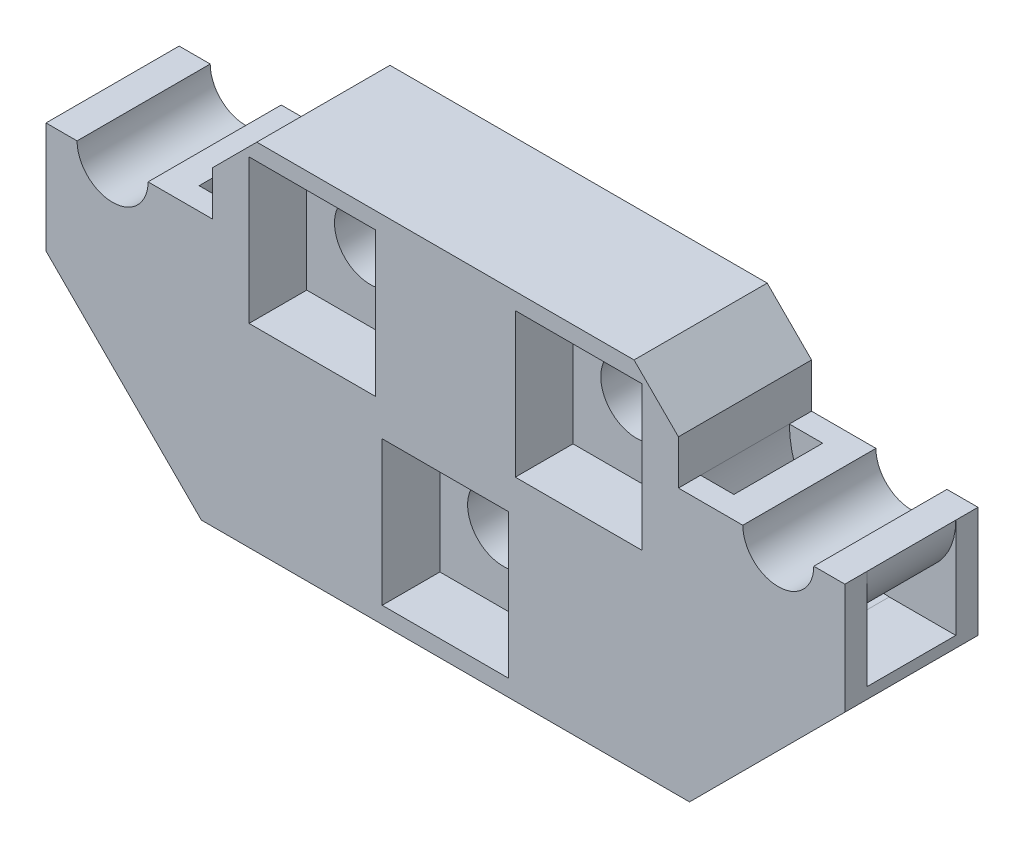
SolidWorks part; units mm, degrees
ref_plane "Front Plane" through (0, 0, 0) normal (0, 0, 1) x (1, 0, 0)
ref_plane "Top Plane" through (0, 0, 0) normal (0, 1, 0) x (1, 0, 0)
ref_plane "Right Plane" through (0, 0, 0) normal (1, 0, 0) x (0, 0, -1)
sketch "Sketch1" plane through (0, 0, 0) normal (0, 0, 1) x (1, 0, 0)
  line L1 (321.5816, 91.95) -> (357.5816, 91.95)
  line L2 (321.5816, 91.95) -> (321.5816, 75.95)
  line L3 (321.5816, 75.95) -> (357.5816, 75.95)
  line L4 (357.5816, 91.95) -> (357.5816, 75.95)
  dimension "D1" = 36
  dimension "D2" = 16
extrude "Boss-Extrude1" add sketch "Sketch1" along normal blind 6
sketch "Sketch2" plane through (0, 0, 6) normal (0, 0, 1) x (1, 0, 0)
  line L0 (357.5816, 91.95) -> (321.5816, 91.95) construction
  line L1 (357.5816, 75.95) -> (357.5816, 91.95) construction
  line L2 (321.5816, 91.95) -> (321.5816, 75.95) construction
  circle A0 centre (333.5816, 87.95) radius 1.6
  circle A1 centre (345.5816, 87.95) radius 1.6
  circle A2 centre (339.5816, 79.95) radius 1.6
  dimension "D1" = 3.2
  dimension "D2" = 3.2
  dimension "D3" = 3.2
  dimension "D4" = 4
  dimension "D5" = 4
  dimension "D6" = 8
  dimension "D7" = 12
  dimension "D8" = 12
  dimension "D9" = 18
extrude "Cut-Extrude1" cut sketch "Sketch2" against normal blind 6
chamfer "Chamfer1" distance 7 angle 45 2 edges at (357.5816, 75.95, 3) (321.5816, 75.95, 3)
sketch "Sketch4" plane through (0, 0, 6) normal (0, 0, 1) x (1, 0, 0)
  line L0 (357.5816, 91.95) -> (321.5816, 91.95) construction
  line L1 (321.5816, 91.95) -> (321.5816, 82.95) construction
  line L2 (357.5816, 82.95) -> (357.5816, 91.95) construction
  circle A0 centre (324.5816, 87.95) radius 1.6
  circle A1 centre (354.5816, 87.95) radius 1.6
  dimension "D1" = 3.2
  dimension "D2" = 3.2
  dimension "D3" = 4
  dimension "D4" = 3
  dimension "D5" = 3
  dimension "D6" = 4
extrude "Cut-Extrude2" cut sketch "Sketch4" against normal blind 6
sketch "Sketch5" plane through (0, 0, 6) normal (0, 0, 1) x (1, 0, 0)
  line L0 (321.5816, 91.95) -> (321.5816, 82.95) construction
  line L1 (321.5816, 87.95) -> (329.0816, 87.95)
  line L2 (321.5816, 87.95) -> (321.5816, 91.95)
  line L3 (321.5816, 91.95) -> (329.0816, 91.95)
  line L4 (329.0816, 87.95) -> (329.0816, 91.95)
  line L5 (357.5816, 91.95) -> (321.5816, 91.95) construction
  line L6 (357.5816, 82.95) -> (357.5816, 91.95) construction
  line L7 (357.5816, 87.95) -> (350.0816, 87.95)
  line L8 (357.5816, 87.95) -> (357.5816, 91.95)
  line L9 (357.5816, 91.95) -> (350.0816, 91.95)
  line L10 (350.0816, 87.95) -> (350.0816, 91.95)
  dimension "D1" = 7.5
  dimension "D2" = 7.5
extrude "Cut-Extrude3" cut sketch "Sketch5" against normal blind 6
chamfer "Chamfer2" distance 2 angle 45 2 edges at (350.0816, 91.95, 3) (329.0816, 91.95, 3)
sketch "Sketch6" plane through (0, 87.95, 0) normal (0, 1, 0) x (1, 0, 0)
  line L0 (329.0816, -6) -> (329.0816, 0) construction
  line L1 (329.0816, -1) -> (327.4816, -1)
  line L2 (329.0816, -1) -> (329.0816, -5)
  line L3 (329.0816, -5) -> (327.4816, -5)
  line L4 (327.4816, -1) -> (327.4816, -5)
  line L5 (350.0816, 0) -> (350.0816, -6) construction
  line L6 (350.0816, -1) -> (351.5816, -1)
  line L7 (350.0816, -1) -> (350.0816, -5)
  line L8 (350.0816, -5) -> (351.5816, -5)
  line L9 (351.5816, -1) -> (351.5816, -5)
  line L10 (326.1816, -6) -> (329.0816, -6) construction
  line L11 (350.0816, -6) -> (352.9816, -6) construction
  dimension "D1" = 4
  dimension "D2" = 1.6
  dimension "D3" = 1
  dimension "D4" = 4
  dimension "D5" = 1.5
  dimension "D6" = 1
extrude "Cut-Extrude4" cut sketch "Sketch6" against normal blind 3
sketch "Sketch7" plane through (357.5816, 0, 0) normal (1, 0, 0) x (0, 0, -1)
  line L0 (0, 82.95) -> (0, 87.95) construction
  line L1 (-5, 84.95) -> (-1, 84.95)
  line L2 (-5, 84.95) -> (-5, 83.45)
  line L3 (-5, 83.45) -> (-1, 83.45)
  line L4 (-1, 84.95) -> (-1, 83.45)
  line L5 (0, 87.95) -> (-6, 87.95) construction
  dimension "D1" = 4
  dimension "D2" = 1.5
  dimension "D3" = 1
  dimension "D4" = 3
extrude "Cut-Extrude6" cut sketch "Sketch7" against normal up to surface (7.5 mm away) up to face at (350.0816, 87.7, 3)
fillet "Fillet1" radius 3 1 edges at (351.5816, 84.95, 3)
fillet "Fillet2" radius 3 1 edges at (357.5816, 84.95, 3)
sketch "Sketch8" plane through (321.5816, 0, 0) normal (-1, 0, 0) x (0, 0, 1)
  line L0 (0, 87.95) -> (6, 87.95) construction
  line L1 (5, 84.95) -> (1, 84.95)
  line L2 (5, 84.95) -> (5, 83.45)
  line L3 (5, 83.45) -> (1, 83.45)
  line L4 (1, 84.95) -> (1, 83.45)
  line L5 (6, 87.95) -> (6, 82.95) construction
  dimension "D1" = 1.5
  dimension "D2" = 3
  dimension "D3" = 1
  dimension "D4" = 4
extrude "Cut-Extrude7" cut sketch "Sketch8" against normal up to surface (7.5 mm away) up to face at (329.0816, 87.7, 3)
fillet "Fillet3" radius 3 2 edges at (327.4816, 84.95, 3) (321.5816, 84.95, 3)
sketch "Sketch10" plane through (0, 0, 6) normal (0, 0, 1) x (1, 0, 0)
  line L1 (330.7316, 91.2) -> (336.4316, 91.2)
  line L2 (330.7316, 91.2) -> (330.7316, 84.7)
  line L3 (330.7316, 84.7) -> (336.4316, 84.7)
  line L4 (336.4316, 91.2) -> (336.4316, 84.7)
  line L5 (342.7316, 91.2) -> (348.4316, 91.2)
  line L6 (342.7316, 91.2) -> (342.7316, 84.7)
  line L7 (342.7316, 84.7) -> (348.4316, 84.7)
  line L8 (348.4316, 91.2) -> (348.4316, 84.7)
  line L9 (336.7316, 83.2) -> (342.4316, 83.2)
  line L10 (336.7316, 83.2) -> (336.7316, 76.7)
  line L11 (336.7316, 76.7) -> (342.4316, 76.7)
  line L12 (342.4316, 83.2) -> (342.4316, 76.7)
  circle A0 centre (333.5816, 87.95) radius 1.6 construction
  circle A1 centre (345.5816, 87.95) radius 1.6 construction
  circle A2 centre (339.5816, 79.95) radius 1.6 construction
  dimension "D9" = 2.85
  dimension "D10" = 3.25
  dimension "D1" = 6.5
  dimension "D2" = 5.7
  dimension "D3" = 5.7
  dimension "D4" = 6.5
  dimension "D5" = 6.5
  dimension "D6" = 5.7
  dimension "D7" = 2.85
  dimension "D8" = 2.85
  dimension "D11" = 3.25
  dimension "D12" = 3.25
extrude "Cut-Extrude8" cut sketch "Sketch10" against normal blind 2.6
fillet "Fillet4" radius 4.5 2 edges at (350.0816, 83.45, 3) (329.0816, 83.45, 3)
